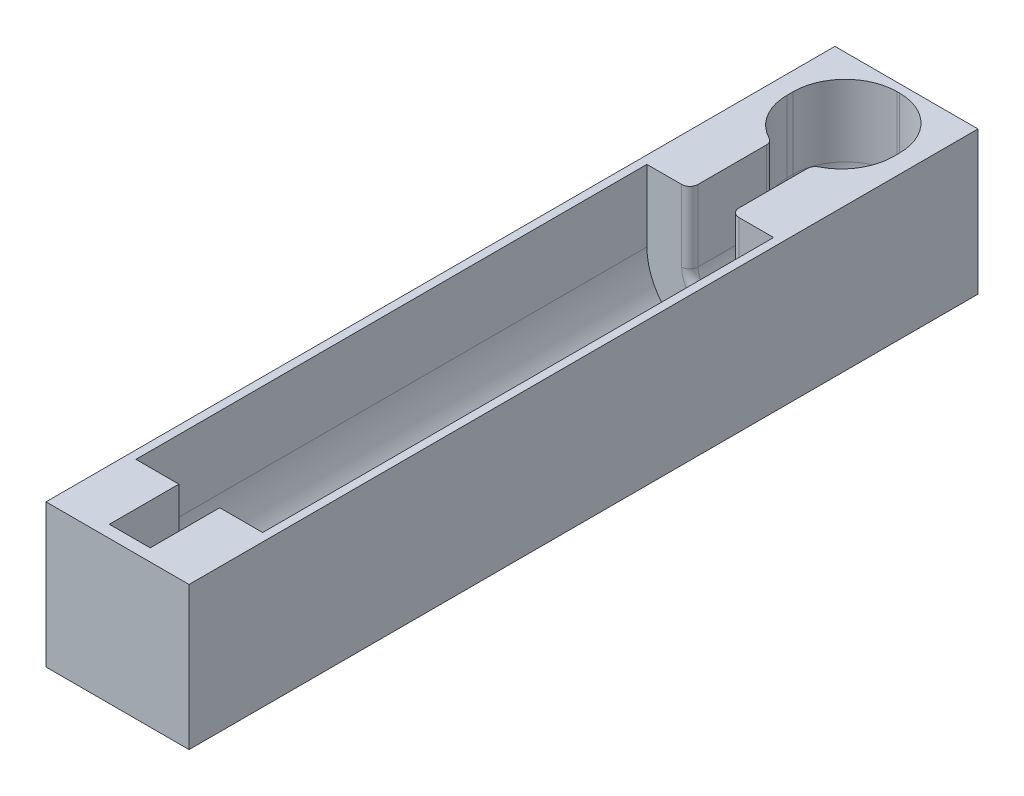
SolidWorks part; units mm, degrees
ref_plane "Front Plane" through (0, 0, 0) normal (0, 0, 1) x (1, 0, 0)
ref_plane "Top Plane" through (0, 0, 0) normal (0, 1, 0) x (1, 0, 0)
ref_plane "Right Plane" through (0, 0, 0) normal (1, 0, 0) x (0, 0, -1)
sketch "Sketch1" plane through (0, 0, 0) normal (0, 0, 1) x (1, 0, 0)
  line L3 (0, -17.5) -> (-17.5, -17.5)
  line L4 (-17.5, -17.5) -> (-17.5, 0)
  line L5 (0, -17.5) -> (17.5, -17.5)
  line L6 (17.5, -17.5) -> (17.5, 0)
  line L8 (-15.5, 0) -> (-15.5, 17.5)
  line L9 (17.5, 0) -> (17.5, 17.5)
  line L10 (15.5, 0) -> (15.5, 17.5)
  line L11 (-17.5, 0) -> (-17.5, 17.5)
  line L12 (-17.5, 17.5) -> (-15.5, 17.5)
  line L13 (15.5, 17.5) -> (17.5, 17.5)
  arc A0 (-15.5, 0) -> (15.5, 0) centre (0, 0) ccw
  dimension "D1" = 31
  dimension "D2" = 17.5
  dimension "D3" = 17.5
  dimension "D4" = 17.5
extrude "Boss-Extrude3" add sketch "Sketch1" along normal blind 125
sketch "Sketch4" plane through (0, 0, 125) normal (0, 0, 1) x (1, 0, 0)
  line L1 (-17.5, 17.5) -> (17.5, 17.5)
  line L2 (-17.5, 17.5) -> (-17.5, -17.5)
  line L3 (-17.5, -17.5) -> (17.5, -17.5)
  line L4 (17.5, 17.5) -> (17.5, -17.5)
extrude "Boss-Extrude4" add sketch "Sketch4" along normal blind 20
sketch "Sketch5" plane through (0, 0, 125) normal (0, 0, -1) x (-1, 0, 0)
  line L0 (-5, 0) -> (-5, 17.5)
  line L1 (-15.5, 17.5) -> (15.5, 17.5) construction
  line L2 (5, 0) -> (5, 17.5)
  line L3 (5, 17.5) -> (-5, 17.5)
  arc A0 (-5, 0) -> (5, 0) centre (0, 0) ccw
  dimension "D1" = 10
extrude "Cut-Extrude2" cut sketch "Sketch5" against normal blind 17
sketch "Sketch6" plane through (0, 0, 0) normal (0, 0, -1) x (-1, 0, 0)
  line L1 (-17.5, 17.5) -> (17.5, 17.5)
  line L2 (-17.5, 17.5) -> (-17.5, -17.5)
  line L3 (-17.5, -17.5) -> (17.5, -17.5)
  line L4 (17.5, 17.5) -> (17.5, -17.5)
extrude "Boss-Extrude5" add sketch "Sketch6" along normal blind 48
sketch "Sketch7" plane through (0, 0, 0) normal (0, 0, 1) x (1, 0, 0)
  line L0 (-5, 0) -> (-5, 17.5)
  line L1 (-15.5, 17.5) -> (15.5, 17.5) construction
  line L2 (5, 0) -> (5, 17.5)
  line L3 (5, 17.5) -> (-5, 17.5)
  arc A0 (-5, 0) -> (5, 0) centre (0, 0) ccw
  dimension "D1" = 10
extrude "Cut-Extrude3" cut sketch "Sketch7" against normal blind 20
sketch "Sketch8" plane through (0, 0, -20) normal (0, 0, 1) x (1, 0, 0)
  line L0 (-13, 0) -> (-13, 27.3394)
  line L1 (13, 0) -> (13, 27.3394)
  line L2 (-13, 27.3394) -> (13, 27.3394)
  arc A0 (-13, 0) -> (13, 0) centre (0, 0) ccw
  dimension "D1" = 26
extrude "Cut-Extrude4" cut sketch "Sketch8" against normal blind 26
fillet "Fillet1" radius 12.7 6 edges at (13, 8.75, -20) (0, -13, -20) (13, 8.75, -46) (0, -13, -46) (-13, 8.75, -20) (-13, 8.75, -46)
fillet "Fillet2" radius 2 6 edges at (5, 8.75, 0) (0, -5, 0) (5, 8.75, -20) (0, -5, -20) (-5, 8.75, 0) (-5, 8.75, -20)
